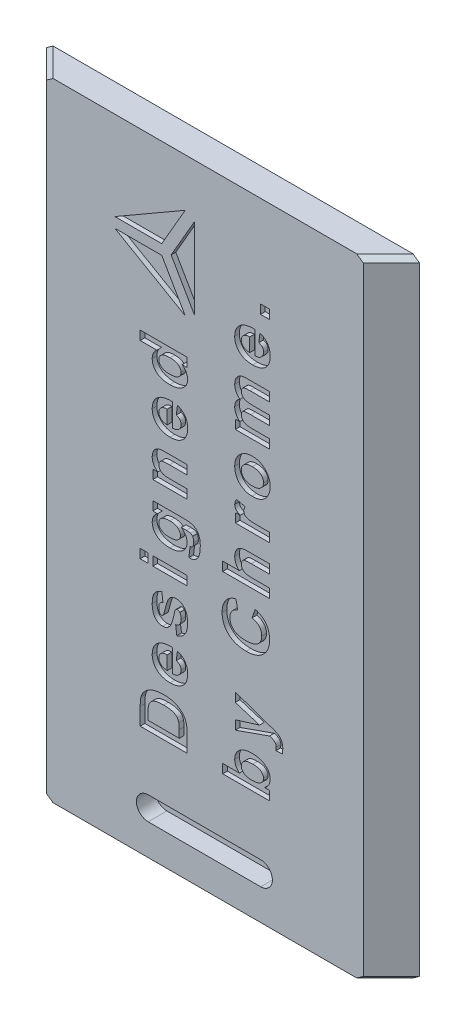
SolidWorks part; units mm, degrees
material "Custom Plastic"
ref_plane "Front Plane" through (0, 0, 0) normal (0, 0, 1) x (1, 0, 0)
ref_plane "Top Plane" through (0, 0, 0) normal (0, 1, 0) x (1, 0, 0)
ref_plane "Right Plane" through (0, 0, 0) normal (1, 0, 0) x (0, 0, -1)
sketch "Sketch1" plane through (0, 0, 0) normal (0, 0, 1) x (1, 0, 0)
  line L1 (0, 0) -> (39.8, 0)
  line L2 (0, 0) -> (0, 66.9)
  line L3 (0, 66.9) -> (39.8, 66.9)
  line L4 (39.8, 0) -> (39.8, 66.9)
  dimension "D1" = 39.8
  dimension "D2" = 66.9
extrude "Boss-Extrude1" add sketch "Sketch1" along normal blind 3
sketch "Sketch2" plane through (0, 0, 0) normal (0, -1, 0) x (1, 0, 0)
  line L0 (0, 0) -> (0, 3)
  line L1 (0, 3) -> (3, 3)
  line L2 (0, 3) -> (39.8, 3) construction
  line L3 (3, 3) -> (0, 0)
  line L4 (39.8, 0) -> (39.8, 3)
  line L5 (39.8, 3) -> (36.8, 3)
  line L6 (36.8, 3) -> (39.8, 0)
  dimension "D1" = 135
  dimension "D2" = 135
extrude "Cut-Extrude2" cut sketch "Sketch2" against normal blind 68
sketch "Sketch3" plane through (0, 0, 3) normal (0, 0, 1) x (1, 0, 0)
  line L0 (18, 62.6863) -> (18, 11.2021) construction
  line L1 (26.8, 62.6863) -> (26.8, 11.2021) construction
  line L2 (3, 66.9) -> (3, 0) construction
  line L3 (36.8, 66.9) -> (36.8, 0) construction
  line L4 (13, 0) -> (13, 66.9) construction
  line L5 (3, 0) -> (36.8, 0) construction
  line L6 (36.8, 66.9) -> (3, 66.9) construction
  line L7 (36.8, 56.9) -> (26.663, 56.9) construction
  line L8 (16.3, 56.9) -> (18.8, 61.2301)
  line L9 (18.8, 61.2301) -> (18.8, 52.5699)
  line L10 (18.8, 52.5699) -> (16.3, 56.9)
  line L11 (10.3, 57.44) -> (15.3, 57.44)
  line L12 (15.3, 57.44) -> (17.8, 61.7701)
  line L13 (17.8, 61.7701) -> (10.3, 57.44)
  line L14 (10.3, 56.36) -> (15.3, 56.36)
  line L15 (15.3, 56.36) -> (17.8, 52.0299)
  line L16 (17.8, 52.0299) -> (10.3, 56.36)
  line L17 (18.8, 47.3611) -> (18.8, 62.4343) construction
  text T0 "Designed" font "Arial" height 5
  text T1 "by Chrome." font "Arial" height 5
  point P11 (18.8, 56.9)
  point P29 (26.3, 8.786)
  point P30 (19, 8.786)
  point P31 (18.8, 11.2021)
  point P32 (25.8, 11.2021)
  dimension "D1" = 10
  dimension "D2" = 15
  dimension "D3" = 10
  dimension "D4" = 10
  dimension "D5" = 30
  dimension "D6" = 1
  dimension "D7" = 2.5
  dimension "D8" = 0.54
  dimension "D9" = 1
  dimension "D10" = 5
  dimension "D11" = 0.54
  dimension "D12" = 18
  dimension "D13" = 5
  dimension "D14" = 5
  dimension "D15" = 5
  dimension "D16" = 5
extrude "Cut-Extrude3" cut sketch "Sketch3" against normal blind 0.5
sketch "Sketch4" plane through (0, 0, 3) normal (0, 0, 1) x (1, 0, 0)
  line L1 (13.85, 5.8071) -> (25.85, 5.8071)
  line L3 (13.85, 3.3071) -> (25.85, 3.3071)
  arc A0 (13.85, 3.3071) -> (13.85, 5.8071) centre (13.85, 4.5571) cw
  arc A1 (25.85, 5.8071) -> (25.85, 3.3071) centre (25.85, 4.5571) cw
  dimension "D1" = 2.5
  dimension "D2" = 12
extrude "Cut-Extrude4" cut sketch "Sketch4" against normal blind 2
chamfer "Chamfer3" distance 0.5 angle 45 2 edges at (38.3, 66.9, 1.5) (1.5, 66.9, 1.5)
chamfer "Chamfer4" distance 0.5 angle 45 2 edges at (38.3, 0, 1.5) (1.5, 0, 1.5)
